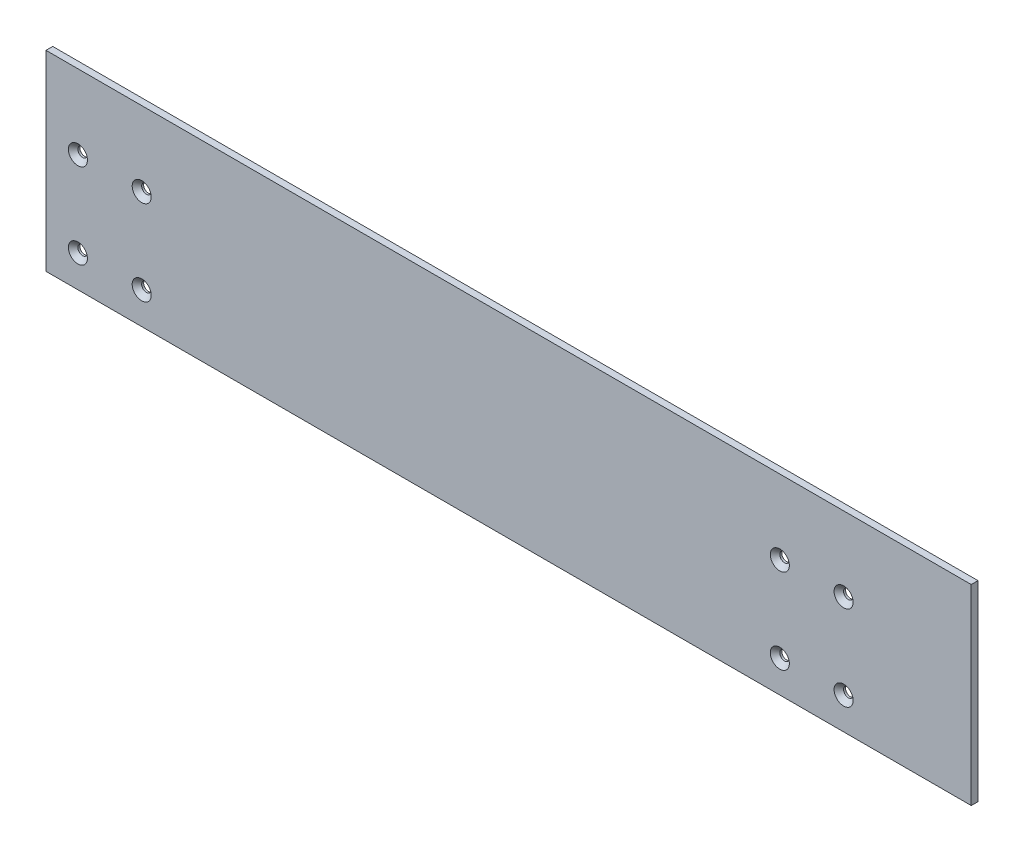
SolidWorks part; units mm, degrees
ref_plane "Front Plane" through (0, 0, 0) normal (0, 0, 1) x (1, 0, 0)
ref_plane "Top Plane" through (0, 0, 0) normal (0, 1, 0) x (1, 0, 0)
ref_plane "Right Plane" through (0, 0, 0) normal (1, 0, 0) x (0, 0, -1)
sketch "Sketch2" plane through (0, 0, 0) normal (0, 0, 1) x (1, 0, 0)
  line L1 (-217.5, -45) -> (217.5, -45)
  line L2 (-217.5, -45) -> (-217.5, 45)
  line L3 (-217.5, 45) -> (217.5, 45)
  line L4 (217.5, -45) -> (217.5, 45)
  line L5 (-217.5, -45) -> (217.5, 45) construction
  line L6 (-217.5, 45) -> (217.5, -45) construction
  point P0 (0, 0)
  dimension "D1" = 435
  dimension "D2" = 90
extrude "Boss-Extrude1" add sketch "Sketch2" along normal blind 3.175
hole_wizard "CSK for M4 SFHCS1" positions "Sketch3" profile "Sketch4" countersink size "M4" standard "ANSI Metric" end condition through all
sketch "Sketch3" plane through (0, 0, 3.175) normal (0, 0, 1) x (1, 0, 0)
  line L1 (-202.5, -30) -> (-172.5, -30)
  line L2 (-202.5, -30) -> (-202.5, 10)
  line L3 (-202.5, 10) -> (-172.5, 10)
  line L4 (-172.5, -30) -> (-172.5, 10)
  line L5 (-202.5, -30) -> (-172.5, 10) construction
  line L6 (-202.5, 10) -> (-172.5, -30) construction
  line L7 (-217.5, 45) -> (-217.5, -45) construction
  line L9 (-217.5, -45) -> (217.5, -45) construction
  point P1 (-172.5, 10)
  point P48 (-202.5, -30)
  point P49 (-202.5, 10)
  point P50 (-172.5, -30)
  point P53 (-187.5, -10)
  point P83 (157.5, 10)
  point P84 (127.5, -30)
  point P85 (127.5, 10)
  point P86 (157.5, -30)
  dimension "D1" = 30
  dimension "D2" = 40
  dimension "D3" = 30
  dimension "D4" = 35
sketch "Sketch4" plane through (-172.5, 10, 3.175) normal (1, 0, 0) x (0, -1, 0)
  line L0 (0, 0) -> (0, 3.175)
  line L1 (0, 3.175) -> (2.25, 3.175)
  line L2 (2.25, 3.175) -> (2.25, 2.23)
  line L3 (2.25, 2.23) -> (4.48, 0)
  line L5 (4.48, 0) -> (0, 0)
  line L6 (-2.25, 2.23) -> (-4.48, 0) construction
  line L11 (0, -6.35) -> (0, 107.95) construction
  dimension "Thru Hole Dia." = 4.5
  dimension "Thru Hole Depth" = 3.175
  dimension "Near C'Sink Dia." = 8.96
  dimension "Near C'Sink Angle" = 90
